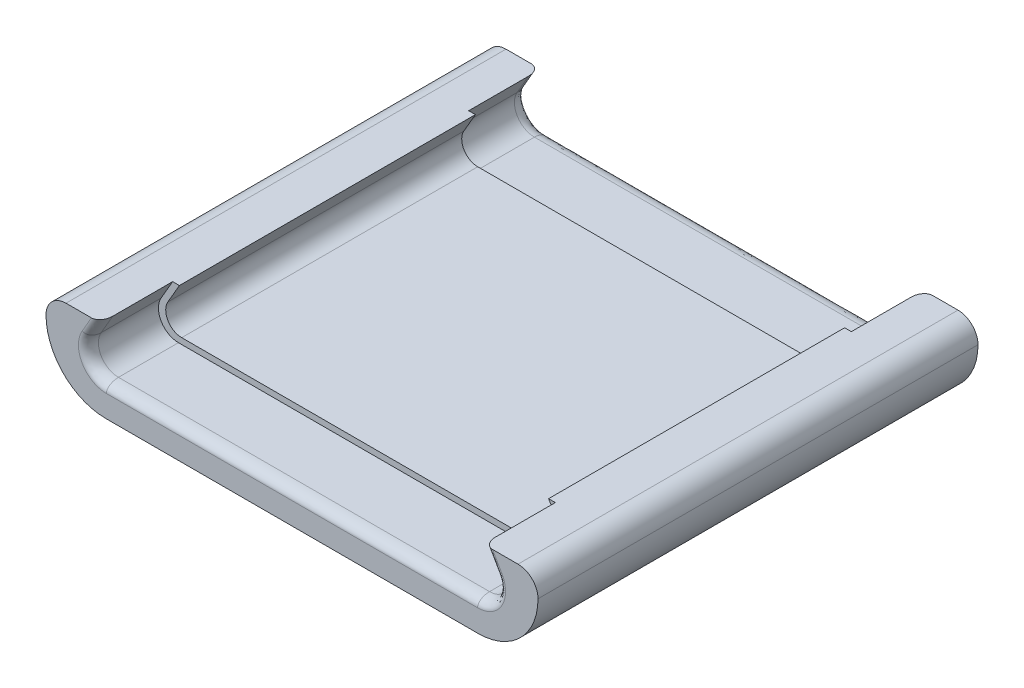
SolidWorks part; units mm, degrees
ref_plane "Front Plane" through (0, 0, 0) normal (0, 0, 1) x (1, 0, 0)
ref_plane "Top Plane" through (0, 0, 0) normal (0, 1, 0) x (1, 0, 0)
ref_plane "Right Plane" through (0, 0, 0) normal (1, 0, 0) x (0, 0, -1)
sketch "Sketch1" plane through (0, 0, 0) normal (0, 1, 0) x (1, 0, 0)
  line L1 (-7.7734, 74.2993) -> (115.2266, 74.2993)
  line L2 (-7.7734, 74.2993) -> (-7.7734, 184.2993)
  line L3 (-7.7734, 184.2993) -> (115.2266, 184.2993)
  line L4 (115.2266, 74.2993) -> (115.2266, 184.2993)
  dimension "D1" = 110
  dimension "D2" = 123
extrude "Boss-Extrude1" add sketch "Sketch1" along normal blind 20
sketch "Sketch5" plane through (0, 0, -74.2993) normal (0, 0, 1) x (1, 0, 0)
  line L0 (5.8934, 20) -> (101.5597, 20)
  line L2 (-1.3234, 7.5) -> (108.7766, 7.5)
  line L9 (-7.7734, 20) -> (-7.7734, 0) construction
  line L10 (115.2266, 20) -> (115.2266, 0) construction
  line L12 (-1.3234, 7.5) -> (5.8934, 20)
  line L14 (108.7766, 7.5) -> (101.5597, 20)
  dimension "D1" = 110.1
  dimension "D2" = 6.45
  dimension "D3" = 6.45
  dimension "D4" = 60
  dimension "D5" = 60
  dimension "D6" = 14.4338
  dimension "D7" = 14.4338
extrude "Cut-Extrude3" cut sketch "Sketch5" against normal blind 150
fillet "Fillet2" radius 5 2 edges at (108.7766, 7.5, -129.2993) (-1.3234, 7.5, -129.2993)
fillet "Fillet5" radius 15 2 edges at (-7.7734, 0, -129.2993) (115.2266, 0, -129.2993)
fillet "Fillet6" radius 2 5 edges at (4.4501, 17.5, -74.2993) (103.0031, 17.5, -74.2993) (3.0067, 10, -74.2993) (104.4464, 10, -74.2993) (53.7266, 7.5, -74.2993) second distance 3 first distance on face at (53.7266, 12.1906, -74.2993)
fillet "Fillet7" radius 3 5 edges at (4.4501, 17.5, -184.2993) (103.0031, 17.5, -184.2993) (3.0067, 10, -184.2993) (104.4464, 10, -184.2993) (53.7266, 7.5, -184.2993) second distance 2 first distance on face at (4.8109, 18.125, -104.0493) first distance on face at (103.3639, 16.875, -157.5493) first distance on face at (4.0892, 11.875, -130.7993) first distance on face at (102.2814, 10, -130.7993) first distance on face at (42.1291, 7.5, -130.7993)
fillet "Fillet8" radius 5 2 edges at (-7.7734, 20, -129.2993) (115.2266, 20, -129.2993)
sketch "Sketch6" plane through (0, 0, -184.2993) normal (0, 0, -1) x (-1, 0, 0)
  line L1 (-110.2266, 20) -> (2.7734, 20)
  line L2 (-110.2266, 20) -> (-110.2266, 5.5)
  line L3 (-110.2266, 5.5) -> (2.7734, 5.5)
  line L4 (2.7734, 20) -> (2.7734, 5.5)
  dimension "D1" = 113
extrude "Boss-Extrude3" add sketch "Sketch6" against normal blind 64 from offset 18 offset against normal yes
sketch "Sketch8" plane through (0, 0, -102.2993) normal (0, 0, 1) x (1, 0, 0)
  line L0 (1.2266, 9) -> (106.2266, 9)
  line L1 (106.2266, 9) -> (99.8757, 20)
  line L2 (99.8757, 20) -> (7.5774, 20)
  line L3 (7.5774, 20) -> (1.2266, 9)
  line L4 (7.3368, 7.5) -> (100.1163, 7.5) construction
  line L5 (5.8934, 20) -> (101.5597, 20) construction
  dimension "D1" = 105
  dimension "D2" = 60
  dimension "D3" = 60
  dimension "D4" = 105
  dimension "D5" = 2.55
  dimension "D6" = 11
  dimension "D7" = 0
extrude "Cut-Extrude4" cut sketch "Sketch8" against normal blind 64
fillet "Fillet10" radius 4 2 edges at (106.2266, 9, -134.2993) (1.2266, 9, -134.2993)
sketch "Sketch9" plane through (0, 0, -102.2993) normal (0, 0, 1) x (1, 0, 0)
  line L0 (8.1548, 9) -> (99.2984, 9)
  line L1 (7.3368, 7.5) -> (100.1163, 7.5)
  line L2 (5.8934, 20) -> (7.5774, 20)
  line L3 (101.5597, 20) -> (99.8757, 20)
  line L4 (101.5597, 20) -> (104.4464, 15)
  line L5 (5.8934, 20) -> (3.0067, 15)
  line L6 (7.5774, 20) -> (4.6907, 15)
  line L7 (99.8757, 20) -> (102.7625, 15)
  line L16 (101.5597, 20) -> (99.8757, 20)
  line L17 (99.8757, 20) -> (102.7625, 15)
  line L18 (99.2984, 9) -> (8.1548, 9)
  line L19 (4.6907, 15) -> (7.5774, 20)
  line L20 (7.5774, 20) -> (5.8934, 20)
  line L21 (5.8934, 20) -> (3.0067, 15)
  line L22 (7.3368, 7.5) -> (100.1163, 7.5)
  line L23 (104.4464, 15) -> (101.5597, 20)
  arc A1 (2.9908, 14.9723) -> (7.3368, 7.5) centre (7.3368, 12.5) ccw
  arc A2 (3.0067, 15) -> (7.3368, 7.5) centre (7.3368, 12.5) ccw construction
  arc A3 (4.6907, 15) -> (8.1548, 9) centre (8.1548, 13) ccw
  arc A4 (102.7625, 15) -> (99.2984, 9) centre (99.2984, 13) cw
  arc A5 (104.4464, 15) -> (100.1163, 7.5) centre (100.1163, 12.5) cw
  arc A10 (99.2984, 9) -> (102.7625, 15) centre (99.2984, 13) ccw
  arc A11 (4.6907, 15) -> (8.1548, 9) centre (8.1548, 13) ccw
  arc A12 (3.0067, 15) -> (7.3368, 7.5) centre (7.3368, 12.5) ccw
  arc A13 (100.1163, 7.5) -> (104.4464, 15) centre (100.1163, 12.5) ccw
  arc A16 (3.0067, 15) -> (2.9908, 14.9723) centre (7.3368, 12.5) ccw
  dimension "D1" = 0
extrude "Boss-Extrude4" add sketch "Sketch9" along normal blind 10
